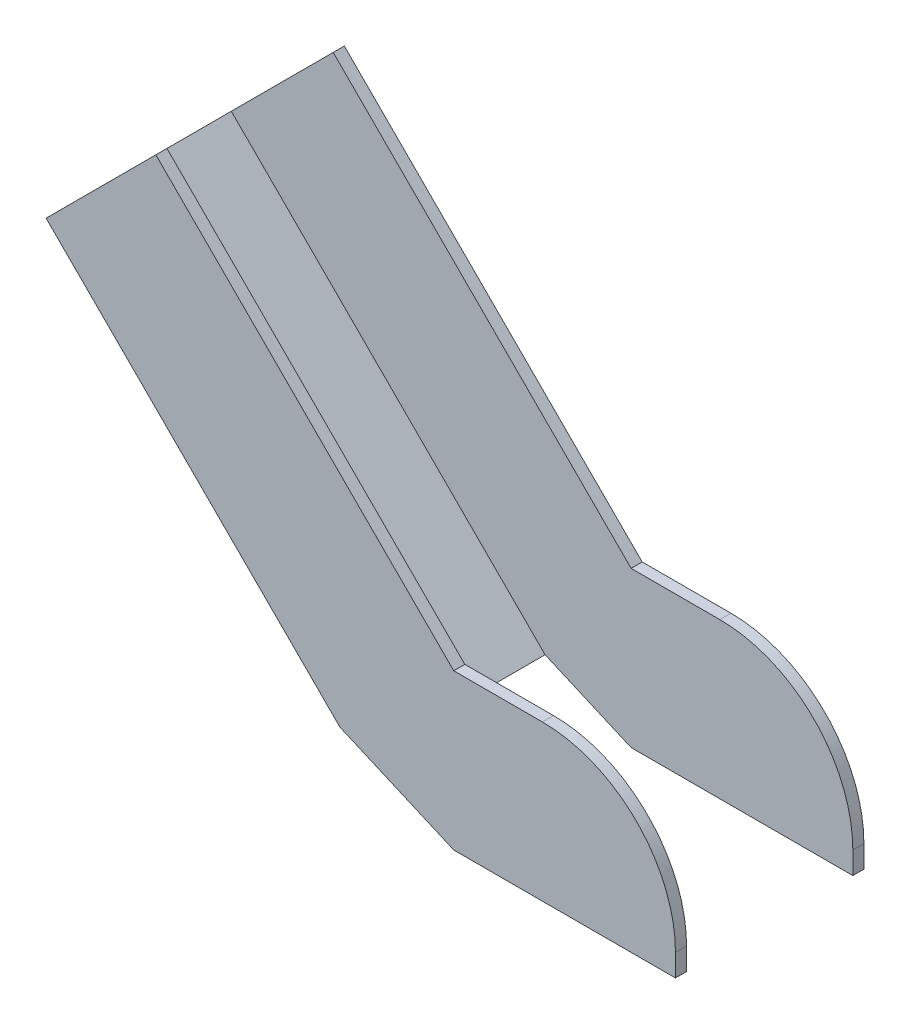
SolidWorks part; units mm, degrees
ref_plane "Front Plane" through (0, 0, 0) normal (0, 0, 1) x (1, 0, 0)
ref_plane "Top Plane" through (0, 0, 0) normal (0, 1, 0) x (1, 0, 0)
ref_plane "Right Plane" through (0, 0, 0) normal (1, 0, 0) x (0, 0, -1)
sketch "Sketch1" plane through (0, 0, 0) normal (0, 0, 1) x (1, 0, 0)
  line L0 (-30, 0) -> (-50, 0)
  line L1 (-50, 0) -> (-117.1751, 67.1751)
  line L2 (-117.1751, 67.1751) -> (-141.9239, 42.4264)
  line L3 (-141.9239, 42.4264) -> (-75.6482, -23.8493)
  line L4 (-75.6482, -23.8493) -> (-50, -35)
  line L5 (-50, -35) -> (0, -35)
  line L6 (0, -35) -> (0, -30)
  arc A0 (-30, 0) -> (0, -30) centre (-30, -30) cw
  point P10 (0, 0)
  dimension "D6" = 30
  dimension "D1" = 95
  dimension "D2" = 35
  dimension "D3" = 35
  dimension "D4" = 50
  dimension "D5" = 50
extrude "Boss-Extrude1" add sketch "Sketch1" along normal blind 42.5
shell "Shell3" thickness 2.5 removed face at (0, -32.5, 21.25) removed face at (-40, 0, 21.25) removed face at (-83.5876, 33.5876, 21.25) removed face at (-129.5495, 54.8008, 21.25) removed face at (-11.8934, -11.8934, 21.25) removed face at (-25, -35, 21.25) removed face at (-62.8241, -29.4246, 21.25)
sketch "Sketch2" plane through (0, -32.5, 0) normal (0, 1, 0) x (1, 0, 0)
  line L0 (0, -40) -> (-49.4801, -40)
  line L1 (-49.4801, -40) -> (-49.4801, -2.5)
  line L2 (-49.4801, -2.5) -> (0, -2.5)
  line L3 (0, -2.5) -> (0, -40)
extrude "Cut-Extrude4" cut sketch "Sketch2" against normal blind 36.5 rebuild error yes
sketch "Sketch9" plane through (0, 0, 40) normal (0, 0, -1) x (-1, 0, 0)
  line L0 (49.4801, -32.5) -> (49.4801, -9.3221)
  line L1 (74.2161, -21.7459) -> (49.4801, -21.7459)
  line L2 (74.2161, -21.7459) -> (49.4801, -32.5)
